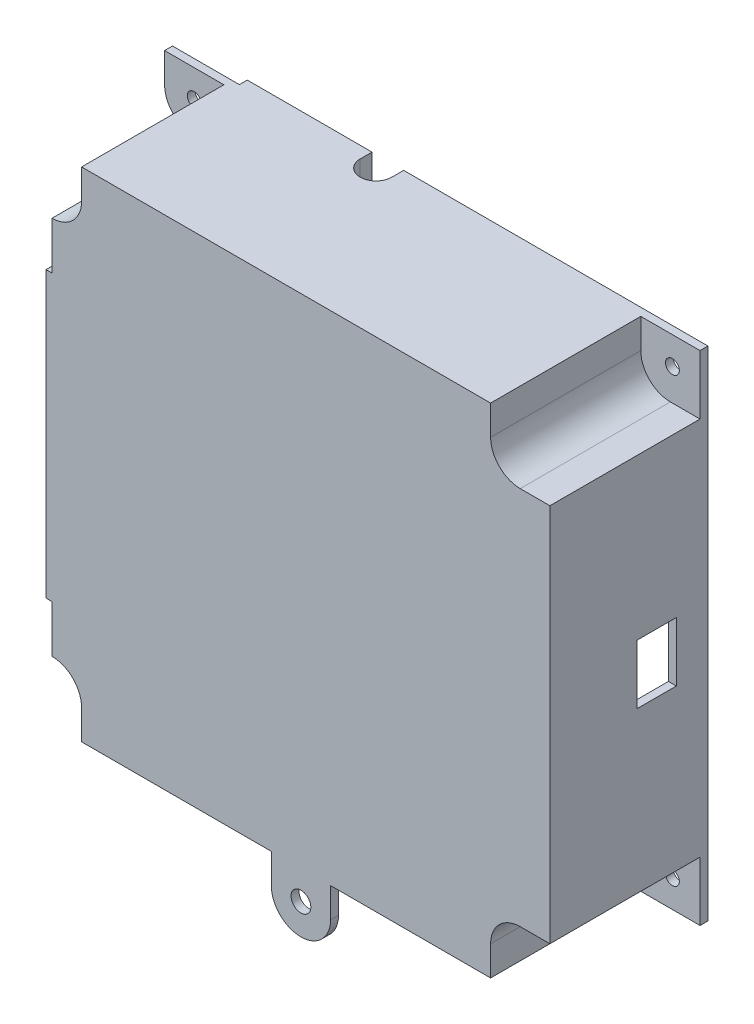
SolidWorks part; units mm, degrees
ref_plane "Plan de face" through (0, 0, 0) normal (0, 0, 1) x (1, 0, 0)
ref_plane "Plan de dessus" through (0, 0, 0) normal (0, 1, 0) x (1, 0, 0)
ref_plane "Plan de droite" through (0, 0, 0) normal (1, 0, 0) x (0, 0, -1)
sketch "Esquisse1" plane through (0, 0, 0) normal (0, 0, 1) x (1, 0, 0)
  line L1 (-151.4404, 157.0104) -> (-25.4404, 157.0104)
  line L2 (-151.4404, 157.0104) -> (-151.4404, 31.0104)
  line L3 (-151.4404, 31.0104) -> (-25.4404, 31.0104)
  line L4 (-25.4404, 157.0104) -> (-25.4404, 31.0104)
  dimension "D1" = 126
  dimension "D2" = 126
extrude "Boss.-Extru.1" add sketch "Esquisse1" along normal blind 40
sketch "Esquisse2" plane through (0, 0, 40) normal (0, 0, 1) x (1, 0, 0)
  line L0 (-40.4404, 31.0104) -> (-25.4404, 31.0104)
  line L1 (-25.4404, 31.0104) -> (-25.4404, 157.0104) construction
  line L2 (-40.4404, 38.5104) -> (-40.4404, 31.0104)
  line L4 (-151.4404, 31.0104) -> (-25.4404, 31.0104) construction
  line L5 (-32.9404, 46.0104) -> (-25.4404, 46.0104)
  line L6 (-25.4404, 46.0104) -> (-25.4404, 31.0104)
  arc A0 (-32.9404, 46.0104) -> (-40.4404, 38.5104) centre (-32.9404, 38.5104) ccw
  dimension "D1" = 7.5
  dimension "D3" = 15
  dimension "D2" = 7.5
extrude "Enlèv. mat.-Extru.1" cut sketch "Esquisse2" against normal blind 38
sketch "Esquisse4" plane through (0, 0, 2) normal (0, 0, 1) x (1, 0, 0)
  line L0 (-40.4404, 31.0104) -> (-25.4404, 31.0104) construction
  line L1 (-25.4404, 31.0104) -> (-25.4404, 46.0104) construction
  circle A0 centre (-32.4404, 38.0104) radius 1.75
  point P4 (-32.9404, 31.0104)
  dimension "D1" = 3.5
  dimension "D2" = 7
  dimension "D3" = 7
extrude "Enlèv. mat.-Extru.2" cut sketch "Esquisse4" against normal up to next
ref_plane "Plan1" through (0, 94.0104, 0) normal (0, -1, 0) x (-1, 0, 0)
mirror "Symétrie1" about plane through (0, 94.0104, 0) normal (0, -1, 0) of "Enlèv. mat.-Extru.2", "Enlèv. mat.-Extru.1"
ref_plane "Plan2" through (-88.4404, 0, 0) normal (-1, 0, 0) x (0, 0, 1)
sketch "Esquisse10" plane through (0, 0, 40) normal (0, 0, 1) x (1, 0, 0)
  line L0 (-151.4404, 31.0104) -> (-40.4404, 31.0104) construction
  line L2 (-151.4404, 46.0104) -> (-151.4404, 31.0104)
  line L3 (-151.4404, 31.0104) -> (-143.9404, 31.0104)
  line L4 (-143.9404, 31.0104) -> (-143.9404, 38.5104)
  arc A0 (-143.9404, 38.5104) -> (-151.4404, 46.0104) centre (-151.4404, 38.5104) ccw
  dimension "D1" = 15
  dimension "D2" = 7.5
extrude "Enlèv. mat.-Extru.5" cut sketch "Esquisse10" against normal blind 36
mirror "Symétrie3" about plane through (0, 94.0104, 0) normal (0, -1, 0) of "Enlèv. mat.-Extru.5"
shell "Coque1" thickness 2 removed face at (-30.6904, 150.0104, 0)
sketch "Esquisse12" plane through (0, 0, 4) normal (0, 0, 1) x (1, 0, 0)
  line L0 (-158.9404, 31.0104) -> (-158.9404, 38.5104)
  line L1 (-151.4404, 31.0104) -> (-158.9404, 31.0104)
  line L2 (-151.4404, 31.0104) -> (-151.4404, 46.0104)
  arc A0 (-151.4404, 46.0104) -> (-158.9404, 38.5104) centre (-151.4404, 38.5104) ccw
  dimension "D2" = 15
  dimension "D3" = 7.5
extrude "Boss.-Extru.3" add sketch "Esquisse12" against normal blind 2
sketch "Esquisse13" plane through (0, 0, 4) normal (0, 0, 1) x (1, 0, 0)
  line L1 (-158.9404, 31.0104) -> (-143.9404, 31.0104) construction
  circle A0 centre (-151.4404, 38.0104) radius 1.75
  dimension "D1" = 3.5
  dimension "D2" = 7
extrude "Enlèv. mat.-Extru.6" cut sketch "Esquisse13" against normal up to next
sketch "Esquisse27" plane through (0, 0, 0) normal (0, 0, -1) x (-1, 0, 0)
  line L0 (145.8814, 48.1414) -> (149.4404, 48.1414) construction
  line L1 (149.4404, 155.0104) -> (149.4404, 33.0104) construction
  line L2 (149.4404, 33.0104) -> (149.4404, 48.1414)
  line L3 (142.0412, 34.9039) -> (142.0412, 33.0104) construction
  line L5 (149.4404, 33.0104) -> (42.4404, 33.0104) construction
  line L6 (151.4404, 31.0104) -> (25.4404, 31.0104) construction
  line L7 (142.0231, 31.0104) -> (151.4404, 31.0104)
  line L8 (149.4404, 33.0104) -> (142.0412, 33.0104)
  line L9 (142.0412, 33.0104) -> (142.0231, 31.0104)
  line L10 (149.4404, 48.1414) -> (151.4404, 48.1414)
  line L11 (151.4404, 157.0104) -> (151.4404, 39.7604) construction
  line L12 (151.4404, 48.1414) -> (151.4404, 31.0104)
extrude "Enlèv. mat.-Extru.14" cut sketch "Esquisse27" against normal up to surface (2 mm away) up to face at (-154.4909, 37.3526, 2)
mirror "Symétrie5" about plane through (0, 94.0104, 0) normal (0, -1, 0) of "Enlèv. mat.-Extru.14", "Enlèv. mat.-Extru.6", "Boss.-Extru.3"
sketch "Esquisse16" plane through (-151.4404, 0, 0) normal (-1, 0, 0) x (0, 0, 1)
  line L0 (0, 139.8793) -> (0, 48.1414) construction
  line L1 (0, 130.0104) -> (40, 130.0104)
  line L2 (0, 130.0104) -> (0, 58.0104)
  line L3 (0, 58.0104) -> (40, 58.0104)
  line L4 (40, 130.0104) -> (40, 58.0104)
  line L5 (40, 142.0104) -> (40, 46.0104) construction
  line L6 (4, 46.0104) -> (40, 46.0104) construction
  line L7 (4, 142.0104) -> (40, 142.0104) construction
  dimension "D1" = 12
  dimension "D2" = 12
extrude "Enlèv. mat.-Extru.9" cut sketch "Esquisse16" against normal up to surface (2 mm away) up to face at (-149.4404, 94.0104, 10.5)
sketch "Esquisse20" plane through (0, 0, 40) normal (0, 0, 1) x (1, 0, 0)
  line L0 (-143.9404, 31.0104) -> (-40.4404, 31.0104) construction
  line L1 (-80.9404, 31.0104) -> (-95.9404, 31.0104)
  line L2 (-80.9404, 31.0104) -> (-80.9404, 23.5104)
  line L4 (-95.9404, 31.0104) -> (-95.9404, 23.5104)
  line L5 (-88.4404, 22) -> (-88.4404, -22) construction
  arc A0 (-80.9404, 23.5104) -> (-95.9404, 23.5104) centre (-88.4404, 23.5104) cw
  dimension "D2" = 15
  dimension "D3" = 7.5
extrude "Boss.-Extru.5" add sketch "Esquisse20" against normal blind 2
sketch "Esquisse21" plane through (0, 0, 40) normal (0, 0, 1) x (1, 0, 0)
  line L0 (-95.9404, 31.0104) -> (-95.9404, 23.5104) construction
  circle A0 centre (-88.4404, 23.7604) radius 2.5
  arc A1 (-95.9404, 23.5104) -> (-80.9404, 23.5104) centre (-88.4404, 23.5104) ccw construction
  point P7 (-88.4404, 16.0104)
  dimension "D1" = 5
  dimension "D2" = 7.5
  dimension "D3" = 7.75
extrude "Enlèv. mat.-Extru.11" cut sketch "Esquisse21" against normal up to next
sketch "Esquisse23" plane through (0, 0, 38) normal (0, 0, -1) x (-1, 0, 0)
  line L0 (25.4404, 46.0104) -> (25.4404, 142.0104) construction
  line L1 (80.9404, 31.0104) -> (40.4404, 31.0104) construction
  circle A0 centre (40.4404, 81.0104) radius 3
  dimension "D1" = 6
  dimension "D2" = 15
  dimension "D3" = 50
extrude "Boss.-Extru.7" add sketch "Esquisse23" along normal blind 10
sketch "Esquisse24" plane through (0, 0, 28) normal (0, 0, -1) x (-1, 0, 0)
  circle A0 centre (40.4404, 81.0104) radius 1
  circle A1 centre (40.4404, 81.0104) radius 3 construction
  dimension "D1" = 2
  dimension "D2" = 0
extrude "Enlèv. mat.-Extru.12" cut sketch "Esquisse24" against normal blind 9
pattern_linear "Répétition linéaire1" count 2 spacing 25 along (0, 1, 0) of "Boss.-Extru.7", "Enlèv. mat.-Extru.12"
pattern_linear "Répétition linéaire2" count 2 spacing 52 along (-1, 0, 0) of "Répétition linéaire1"
sketch "Esquisse25" plane through (-25.4404, 0, 0) normal (1, 0, 0) x (0, 0, -1)
  line L1 (-8, 86.5104) -> (-18, 86.5104)
  line L2 (-8, 86.5104) -> (-8, 101.5104)
  line L3 (-8, 101.5104) -> (-18, 101.5104)
  line L4 (-18, 86.5104) -> (-18, 101.5104)
  line L6 (-40, 46.0104) -> (-40, 142.0104) construction
  line L9 (-2, 31.0104) -> (-40, 31.0104) construction
  dimension "D1" = 22
  dimension "D2" = 10
  dimension "D3" = 15
  dimension "D4" = 55.5
extrude "Enlèv. mat.-Extru.13" cut sketch "Esquisse25" against normal up to next
sketch "Esquisse28" plane through (-149.4404, 0, 0) normal (-1, 0, 0) x (0, 0, 1)
  line L1 (40, 58.0104) -> (38, 58.0104)
  line L2 (40, 58.0104) -> (40, 130.0104)
  line L3 (40, 130.0104) -> (38, 130.0104)
  line L4 (38, 58.0104) -> (38, 130.0104)
extrude "Boss.-Extru.8" add sketch "Esquisse28" along normal blind 3.5
sketch "Esquisse30" plane through (0, 0, 38) normal (0, 0, -1) x (-1, 0, 0)
  line L0 (42.4404, 155.0104) -> (141.9404, 155.0104) construction
  line L1 (96.4404, 155.0104) -> (116.4404, 155.0104)
  line L2 (96.4404, 155.0104) -> (96.4404, 150.0104)
  line L3 (96.4404, 150.0104) -> (116.4404, 150.0104)
  line L4 (116.4404, 155.0104) -> (116.4404, 150.0104)
  line L6 (151.4404, 142.0104) -> (151.4404, 130.0104) construction
  dimension "D1" = 5
  dimension "D2" = 20
  dimension "D3" = 35
extrude "Boss.-Extru.9" add sketch "Esquisse30" along normal up to surface (38 mm away) up to face at (-30.6904, 150.0104, 0)
sketch "Esquisse29" plane through (0, 157.0104, 0) normal (0, 1, 0) x (1, 0, 0)
  line L0 (-151.4404, -4) -> (-151.4404, -40) construction
  line L1 (-110.4404, -3) -> (-110.4404, 0)
  line L2 (-25.4404, 0) -> (-142.0231, 0) construction
  line L3 (-110.4404, 0) -> (-102.4404, 0)
  line L4 (-102.4404, 0) -> (-102.4404, -3)
  arc A0 (-110.4404, -3) -> (-102.4404, -3) centre (-106.4404, -3) ccw
  dimension "D1" = 8
  dimension "D2" = 45
  dimension "D3" = 3
extrude "Enlèv. mat.-Extru.15" cut sketch "Esquisse29" against normal up to next
